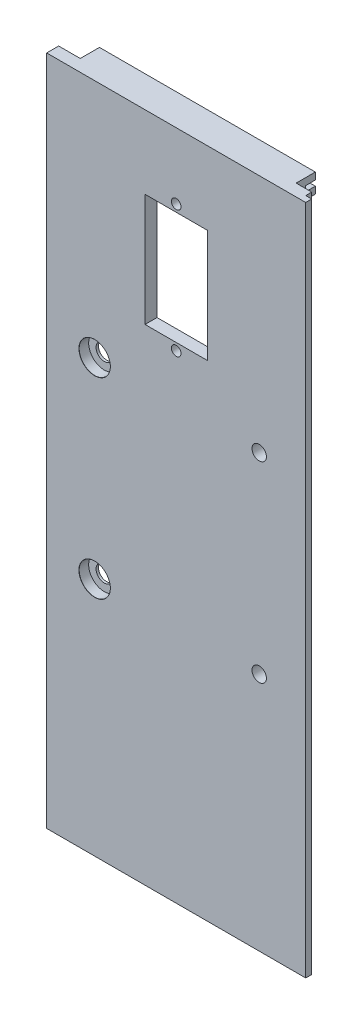
SolidWorks part; units mm, degrees
ref_plane "Plano frontal" through (0, 0, 0) normal (0, 0, 1) x (1, 0, 0)
ref_plane "Plano superior" through (0, 0, 0) normal (0, 1, 0) x (1, 0, 0)
ref_plane "Plano direito" through (0, 0, 0) normal (1, 0, 0) x (0, 0, -1)
sketch "Esboço1" plane through (0, 0, 0) normal (0, 0, 1) x (1, 0, 0)
  line L1 (-15.8914, 40.0685) -> (38.1086, 40.0685)
  line L2 (-15.8914, 40.0685) -> (-15.8914, -99.9315)
  line L3 (-15.8914, -99.9315) -> (38.1086, -99.9315)
  line L4 (38.1086, 40.0685) -> (38.1086, -99.9315)
  dimension "D1" = 54
  dimension "D2" = 140
extrude "Ressalto-extrusão1" add sketch "Esboço1" along normal blind 2.5
sketch "Esboço2" plane through (0, 0, 0) normal (0, 0, -1) x (-1, 0, 0)
  line L0 (-38.1086, 40.0685) -> (15.8914, 40.0685) construction
  line L1 (-33.6086, 40.0685) -> (11.3914, 40.0685)
  line L2 (-33.6086, 40.0685) -> (-33.6086, 36.0685)
  line L3 (-33.6086, 36.0685) -> (11.3914, 36.0685)
  line L4 (11.3914, 40.0685) -> (11.3914, 36.0685)
  line L5 (11.3914, 40.0685) -> (15.8914, 40.0685) construction
  line L6 (-38.1086, 40.0685) -> (-33.6086, 40.0685) construction
  dimension "D1" = 45
  dimension "D2" = 4
extrude "Ressalto-extrusão2" add sketch "Esboço2" along normal blind 4
fillet "Filete1" radius 2 1 edges at (11.1086, 36.0685, 0)
sketch "Esboço3" plane through (0, 0, -4) normal (0, 0, -1) x (-1, 0, 0)
  line L0 (-33.6086, 40.0685) -> (-33.6086, 34.0685) construction
  line L1 (-33.6086, 38.6185) -> (11.3914, 38.6185)
  line L2 (-33.6086, 38.6185) -> (-33.6086, 37.5185)
  line L3 (-33.6086, 37.5185) -> (11.3914, 37.5185)
  line L4 (11.3914, 38.6185) -> (11.3914, 37.5185)
  line L6 (11.3914, 40.0685) -> (11.3914, 38.6185) construction
  line L7 (11.3914, 37.5185) -> (11.3914, 36.0685) construction
  dimension "D1" = 1.1
extrude "Corte-extrusão1" cut sketch "Esboço3" against normal blind 2
sketch "Esboço4" plane through (0, 0, 0) normal (0, 0, -1) x (-1, 0, 0)
  line L0 (-38.1086, -29.9315) -> (15.8914, -29.9315) construction
  line L1 (-38.1086, -99.9315) -> (-38.1086, 40.0685) construction
  line L2 (15.8914, 40.0685) -> (15.8914, -99.9315) construction
  line L3 (-11.1086, 40.0685) -> (-11.1086, -99.9315) construction
  line L4 (11.3914, 40.0685) -> (-33.6086, 40.0685) construction
  line L5 (15.8914, -99.9315) -> (-38.1086, -99.9315) construction
  line L6 (5.8914, 40.0685) -> (5.8914, -99.9315) construction
  circle A0 centre (5.8914, -9.9315) radius 3.9278
  circle A1 centre (5.8914, -49.9315) radius 3.9278
  circle A3 centre (-28.4086, -9.9315) radius 3.9278
  circle A4 centre (-28.4086, -49.9315) radius 3.9278
  dimension "D1" = 10
  dimension "D2" = 20
  dimension "D3" = 9.7
hole_wizard "Rebaixo para parafuso com cabeça redonda de M31" positions "Esboço5" profile "Esboço6" counterbore size "M3" standard "ISO" end condition through all
sketch "Esboço5" plane through (0, 0, 2.5) normal (0, 0, 1) x (1, 0, 0)
  point P0 (-5.8914, -9.9315)
  point P3 (-5.8914, -49.9315)
sketch "Esboço6" plane through (-5.8914, -9.9315, 2.5) normal (1, 0, 0) x (0, -1, 0)
  line L0 (0, 0) -> (0, 6.5)
  line L1 (0, 6.5) -> (1.7, 6.5)
  line L3 (1.7, 6.5) -> (1.7, 2)
  line L4 (3.25, 2) -> (1.7, 2)
  line L5 (3.25, 2) -> (3.25, 0.025)
  line L6 (3.25, 0.025) -> (3.275, 0)
  line L7 (3.275, 0) -> (0, 0)
  line L8 (-3.25, 0.025) -> (-3.275, 0) construction
  line L11 (0, -6.35) -> (0, 107.95) construction
  dimension "Thru Hole Dia." = 3.4
  dimension "Thru Hole Depth" = 6.5
  dimension "C'Bore Dia." = 6.5
  dimension "C'Bore Depth" = 2
  dimension "Near C'Sink Dia." = 6.55
  dimension "Near C'Sink Angle" = 90
sketch "Esboço7" plane through (0, 0, 2.5) normal (0, 0, 1) x (1, 0, 0)
  line L0 (11.1086, 40.0685) -> (11.1086, -99.9315) construction
  line L1 (4.6086, 24.7988) -> (17.6086, 24.7988)
  line L2 (4.6086, 24.7988) -> (4.6086, 1.2988)
  line L3 (4.6086, 1.2988) -> (17.6086, 1.2988)
  line L4 (17.6086, 24.7988) -> (17.6086, 1.2988)
  line L5 (4.6086, 13.0488) -> (17.6086, 13.0488) construction
  circle A0 centre (11.1086, 26.2988) radius 1
  circle A1 centre (11.1086, -0.2012) radius 1
  point P4 (11.1086, 24.7988)
  point P11 (11.1086, 27.2988)
  dimension "D3" = 2
  dimension "D1" = 13
  dimension "D2" = 23.5
  dimension "D4" = 2.5
extrude "Corte-extrusão2" cut sketch "Esboço7" against normal through all contours A0 | L2 L1 L4 L3 | A1
sketch "Esboço8" plane through (0, 0, 0) normal (0, 0, -1) x (-1, 0, 0)
  line L1 (-18.2699, 0) -> (-22.2699, 0)
  line L2 (-18.2699, 0) -> (-18.2699, -60)
  line L3 (-18.2699, -60) -> (-22.2699, -60)
  line L4 (-22.2699, 0) -> (-22.2699, -60)
  dimension "D1" = 4
  dimension "D2" = 60
extrude "Ressalto-extrusão3" add sketch "Esboço8" along normal blind 7.5
sketch "Esboço9" plane through (0, 0, -7.5) normal (0, 0, -1) x (-1, 0, 0)
  line L0 (-18.2699, 0) -> (-22.2699, 0) construction
  line L1 (-21.2699, 0) -> (-19.2699, 0)
  line L2 (-21.2699, 0) -> (-21.2699, -58)
  line L3 (-21.2699, -58) -> (-19.2699, -58)
  line L4 (-19.2699, 0) -> (-19.2699, -58)
  line L5 (-22.2699, -60) -> (-18.2699, -60) construction
  line L6 (-22.2699, 0) -> (-21.2699, 0) construction
  line L7 (-19.2699, 0) -> (-18.2699, 0) construction
  dimension "D1" = 2
  dimension "D2" = 2
extrude "Corte-extrusão3" cut sketch "Esboço9" against normal blind 2
sketch "Esboço11" plane through (0, 0, -7.5) normal (0, 0, -1) x (-1, 0, 0)
  line L0 (-18.2699, -60) -> (-18.2699, 0) construction
  line L1 (-22.2699, -60) -> (-18.2699, -60)
  line L2 (-22.2699, -60) -> (-22.2699, -52)
  line L3 (-22.2699, -52) -> (-18.2699, -52)
  line L4 (-18.2699, -60) -> (-18.2699, -52)
  dimension "D1" = 8
extrude "Ressalto-extrusão4" add sketch "Esboço11" along normal blind 4
sketch "Esboço12" plane through (0, -52, 0) normal (0, 1, 0) x (1, 0, 0)
  line L0 (18.2699, 11.5) -> (22.2699, 11.5) construction
  line L1 (19.2699, 7.5) -> (21.2699, 7.5)
  line L2 (19.2699, 7.5) -> (19.2699, 11.5)
  line L3 (19.2699, 11.5) -> (21.2699, 11.5)
  line L4 (21.2699, 7.5) -> (21.2699, 11.5)
  dimension "D1" = 2
extrude "Corte-extrusão5" cut sketch "Esboço12" against normal blind 6
sketch "Esboço13" plane through (22.2699, 0, 0) normal (1, 0, 0) x (0, 0, -1)
  line L0 (11.5, -58) -> (3.9881, -58) construction
  line L1 (3.9881, -58) -> (7.5, -52) construction
  line L2 (0, 0) -> (0, -60) construction
  circle A0 centre (8.5, -55) radius 1.6
  dimension "D1" = 3.2
  dimension "D2" = 3
  dimension "D3" = 8.5
extrude "Corte-extrusão6" cut sketch "Esboço13" against normal blind 4
fillet "Filete2" radius 2 2 edges at (18.7699, -52, -7.5) (21.7699, -52, -7.5)
ref_plane "Plano1" through (0, 0, -10) normal (0, 0, -1) x (-1, 0, 0)
fillet "Filete3" radius 2 1 edges at (20.2699, -60, 0)
fillet "Filete4" radius 2 2 edges at (18.2699, -31, 0) (22.2699, -31, 0)
sketch "Esboço16" plane through (0, 0, 0) normal (0, 0, -1) x (-1, 0, 0)
  line L0 (15.8914, -99.9315) -> (-38.1086, -99.9315) construction
  line L1 (-38.1086, 40.0685) -> (-36.8586, 40.0685)
  line L2 (-38.1086, 40.0685) -> (-38.1086, -99.9315)
  line L3 (-38.1086, -99.9315) -> (-36.8586, -99.9315)
  line L4 (-36.8586, 40.0685) -> (-36.8586, -99.9315)
  dimension "D1" = 1.25
extrude "Corte-extrusão7" cut sketch "Esboço16" against normal blind 1.25
hole_wizard "Furos-guia com Ø3.0mm2" positions "Esboço17" profile "Esboço18" hole size "Ø3.0" standard "ISO" end condition through all
sketch "Esboço17" plane through (0, 0, 0) normal (0, 0, -1) x (-1, 0, 0)
  point P0 (-28.4086, -9.9315)
  point P3 (-28.4086, -49.9315)
sketch "Esboço18" plane through (28.4086, -9.9315, 0) normal (1, 0, 0) x (0, 1, 0)
  line L0 (0, 0) -> (0, 2.5)
  line L1 (0, 2.5) -> (1.5, 2.5)
  line L2 (1.5, 2.5) -> (1.5, 0.025)
  line L3 (1.5, 0.025) -> (1.525, 0)
  line L5 (1.525, 0) -> (0, 0)
  line L6 (-1.5, 0.025) -> (-1.525, 0) construction
  line L11 (0, -6.35) -> (0, 107.95) construction
  dimension "Thru Hole Dia." = 3
  dimension "Thru Hole Depth" = 2.5
  dimension "Near C'Sink Dia." = 3.05
  dimension "Near C'Sink Angle" = 90
